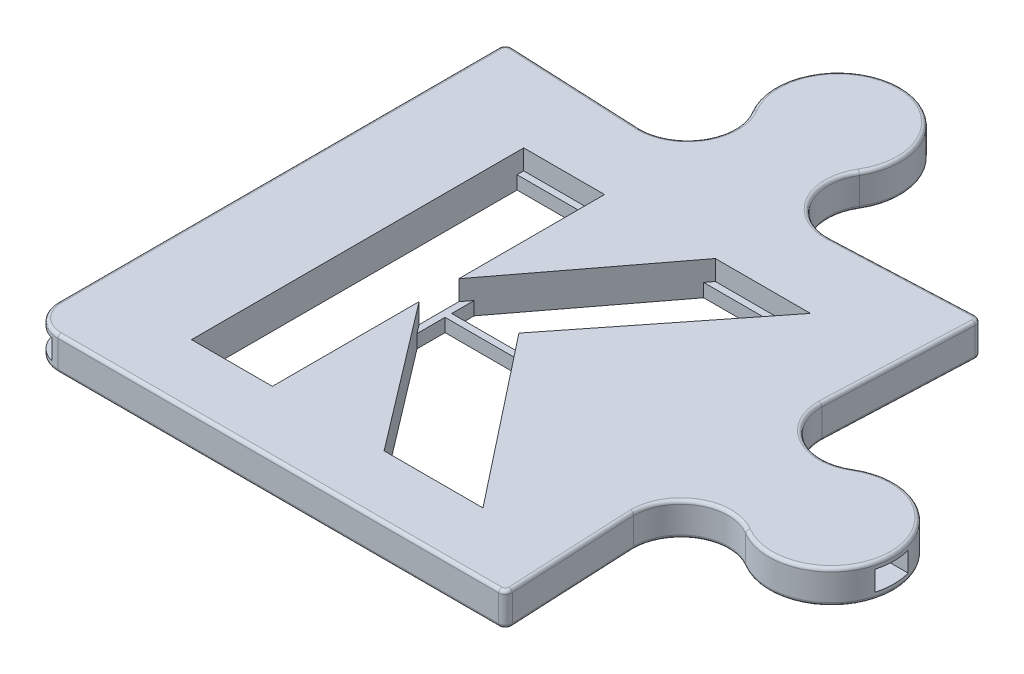
SolidWorks part; units mm, degrees
ref_plane "Front Plane" through (0, 0, 0) normal (0, 0, 1) x (1, 0, 0)
ref_plane "Top Plane" through (0, 0, 0) normal (0, 1, 0) x (1, 0, 0)
ref_plane "Right Plane" through (0, 0, 0) normal (1, 0, 0) x (0, 0, -1)
sketch "Sketch1" plane through (0, 0, 0) normal (0, 1, 0) x (1, 0, 0)
  line L0 (-31, -36) -> (37, -36) construction
  line L1 (-36, 37) -> (-36, -31) construction
  line L2 (-14.1421, 36) -> (-36, 37) construction
  line L3 (37, 37) -> (14.1421, 36) construction
  line L4 (36, 13.1421) -> (37, 37) construction
  line L5 (37, -36) -> (36, -15.1421) construction
  line L6 (-35.4, 36.3719) -> (-35.4, -31)
  line L7 (-36, 36) -> (36, 36) construction
  line L8 (-36, 36) -> (-36, -36) construction
  line L9 (-36, -36) -> (36, -36) construction
  line L10 (36, 36) -> (36, -36) construction
  line L11 (-31, -35.4) -> (36.3705, -35.4)
  line L12 (36.3705, -35.4) -> (35.4, -15.1568)
  line L13 (35.4, 13.155) -> (36.3732, 36.372)
  line L14 (36.3732, 36.372) -> (14.1555, 35.4)
  line L15 (-14.1562, 35.4) -> (-35.4, 36.3719)
  line L16 (-30, -24) -> (30, -24) construction
  line L17 (-30, 29) -> (30, 29) construction
  line L18 (-30, 29) -> (-30, -31) construction
  line L19 (-30, -31) -> (30, -31) construction
  line L20 (30, 29) -> (30, -31) construction
  line L21 (-30, 24) -> (30, 24) construction
  line L22 (-30, 24) -> (-30, -26) construction
  line L23 (-30, -26) -> (30, -26) construction
  line L24 (30, 24) -> (30, -26) construction
  arc A0 (-36, -31) -> (-31, -36) centre (-31, -31) ccw construction
  arc A1 (-14.1421, 36) -> (-8.571, 45.8485) centre (-14.1421, 42.5) ccw construction
  arc A2 (8.571, 45.8485) -> (-8.571, 45.8485) centre (0, 51) ccw construction
  arc A3 (8.571, 45.8485) -> (14.1421, 36) centre (14.1421, 42.5) ccw construction
  arc A4 (36, 13.1421) -> (45.8485, 7.571) centre (42.5, 13.1421) ccw construction
  arc A5 (45.8485, -9.571) -> (45.8485, 7.571) centre (51, -1) ccw construction
  arc A6 (45.8485, -9.571) -> (36, -15.1421) centre (42.5, -15.1421) ccw construction
  arc A7 (-35.4, -31) -> (-31, -35.4) centre (-31, -31) ccw
  arc A8 (46.1576, -9.0567) -> (35.4, -15.1568) centre (42.5, -15.1421) ccw
  arc A9 (46.1576, -9.0567) -> (46.1576, 7.0567) centre (51, -1) ccw
  arc A10 (35.4, 13.155) -> (46.1576, 7.0567) centre (42.5, 13.1421) ccw
  arc A11 (8.0567, 46.1576) -> (14.1555, 35.4) centre (14.1421, 42.5) ccw
  arc A12 (8.0567, 46.1576) -> (-8.0567, 46.1576) centre (0, 51) ccw
  arc A13 (-14.1562, 35.4) -> (-8.0567, 46.1576) centre (-14.1421, 42.5) ccw
  point P32 (36, 0)
  point P34 (0, 36)
  dimension "D5" = 6.5
  dimension "D6" = 10
  dimension "D7" = 6.5
  dimension "D13" = 5
  dimension "D9" = 10
  dimension "D11" = 6.5
  dimension "D12" = 6.5
  dimension "D1" = 72
  dimension "D2" = 1
  dimension "D3" = 1
  dimension "D4" = 15
  dimension "D8" = 1
  dimension "D10" = 35
  dimension "D14" = 15
  dimension "D15" = 36
  dimension "D16" = 1
  dimension "D18" = 60
  dimension "D19" = 60
  dimension "D20" = 5
  dimension "D21" = 6
  dimension "D22" = 5
  dimension "D23" = 50
  dimension "D24" = 2
  dimension "D17" = 0.6
extrude "Boss-Extrude1" add sketch "Sketch1" along normal blind 5
sketch "Sketch6" plane through (0, 0, 0) normal (0, -1, 0) x (1, 0, 0)
  line L0 (-35.4, -36.3719) -> (-35.4, 31) construction
  line L1 (-35.4, 17.9) -> (-27.4, 17.9)
  line L2 (-35.4, 17.9) -> (-35.4, -16.1)
  line L3 (-35.4, -16.1) -> (-27.4, -16.1)
  line L4 (-27.4, 17.9) -> (-27.4, -16.1)
  line L5 (-31, 35.4) -> (36.3705, 35.4) construction
  line L6 (-35.4, 14.65) -> (-30.4, 14.65)
  line L7 (-35.4, 14.65) -> (-35.4, -12.85)
  line L8 (-35.4, -12.85) -> (-30.4, -12.85)
  line L9 (-30.4, 14.65) -> (-30.4, -12.85)
  point P15 (-27.4, 0.9)
  point P16 (-30.4, 0.9)
  line M28 (-35.4, 31) -> (-35.4, -36.3719)
  dimension "D1" = 8
  dimension "D2" = 20.75
  dimension "D3" = 27.5
  dimension "D4" = 5
  dimension "D5" = 34
extrude "Cut-Extrude3" cut sketch "Sketch6" against normal blind 3 from offset 1 contours L6 L9 L8 L3 L4 L1 M28 | L9 L6 L2 L8 region at (-29.8665, 0, 0.9) region at (-32.9, 0, 0.9) offset against normal yes
extrude "Cut-Extrude4" cut sketch "Sketch6<3>" against normal up to next contours L9 L6 L2 L8 region at (-32.9, 0, 0.9)
sketch "Sketch6<3>" plane through (0, 0, 0) normal (0, -1, 0) x (1, 0, 0) same geometry as "Sketch6"
sketch "Sketch8" plane through (0, 0, 0) normal (0, -1, 0) x (1, 0, 0)
  line L1 (-2.5, -51.4) -> (2.5, -51.4)
  line L2 (-2.5, -51.4) -> (-2.5, -60.4)
  line L3 (-2.5, -60.4) -> (2.5, -60.4)
  line L4 (2.5, -51.4) -> (2.5, -60.4)
  line L5 (51.4, 3.5) -> (60.4, 3.5)
  line L6 (51.4, 3.5) -> (51.4, -1.5)
  line L7 (51.4, -1.5) -> (60.4, -1.5)
  line L8 (60.4, 3.5) -> (60.4, -1.5)
  arc A0 (-8.0567, -46.1576) -> (8.0567, -46.1576) centre (0, -51) ccw construction
  arc A1 (46.1576, -7.0567) -> (46.1576, 9.0567) centre (51, 1) ccw construction
  point P4 (0, -60.4)
  point P13 (60.4, 1)
  dimension "D1" = 5
  dimension "D2" = 9
  dimension "D3" = 5
  dimension "D4" = 9
extrude "Cut-Extrude5" cut sketch "Sketch8" against normal blind 3 from offset 1 offset against normal yes
sketch "Sketch9" plane through (0, 0, 0) normal (0, -1, 0) x (1, 0, 0)
  line L0 (-31, 35.4) -> (36.3705, 35.4) construction
  line L1 (-35.4, 14.65) -> (-35.4, 31) construction
  line L2 (-31.7636, 35.3332) -> (-35.4, 31) construction
  line L3 (-33.2571, 29.735) -> (-30.0429, 33.565) construction
  line L4 (-30.0429, 33.565) -> (-33.2571, 29.735) construction
  line L5 (-30.0429, 33.565) -> (-32.7119, 35.8048)
  line L6 (-33.2571, 29.735) -> (-35.926, 31.9747)
  line L7 (-32.7119, 35.8048) -> (-35.926, 31.9747)
  circle A0 centre (-31.65, 31.65) radius 2.5
  arc A1 (-31, 35.4) -> (-35.4, 31) centre (-31, 31) ccw construction
  arc M41 (-31, 35.4) -> (-35.4, 31) centre (-31, 31) ccw
  dimension "D1" = 5
  dimension "D3" = 3.75
  dimension "D4" = 5.6569
  dimension "D2" = 3.75
extrude "Cut-Extrude6" cut sketch "Sketch9" against normal blind 3 from offset 1 contours A0 L5 L6 M41 | A0 L5 region at (-33.6239, 0, 33.3064) region at (-31.65, 0, 31.65) offset against normal yes
sketch "Sketch11" plane through (-35.4, 0, 0) normal (-1, 0, 0) x (0, 0, 1)
  line L0 (-13.155, 0) -> (-36.372, 0) construction
  line L1 (-25.1, 3) -> (-19.1, 3)
  line L2 (-25.1, 3) -> (-25.1, 1.5)
  line L3 (-25.1, 1.5) -> (-19.1, 1.5)
  line L4 (-19.1, 3) -> (-19.1, 1.5)
  line L5 (-16.1, 4) -> (-16.1, 1) construction
  line L6 (35.4, 0) -> (15.1568, 0) construction
  line L7 (20.9, 3) -> (26.9, 3)
  line L8 (20.9, 3) -> (20.9, 1.5)
  line L9 (20.9, 1.5) -> (26.9, 1.5)
  line L10 (26.9, 3) -> (26.9, 1.5)
  line L12 (17.9, 4) -> (17.9, 1) construction
  dimension "D1" = 3
  dimension "D2" = 1.5
  dimension "D3" = 3
  dimension "D4" = 6
  dimension "D5" = 3
  dimension "D6" = 1.5
  dimension "D7" = 6
  dimension "D8" = 3
fillet "Fillet1" radius 0.5 17 edges at (-35.4, 0, 22.825) (-34.1113, 0, 34.1113) (2.6853, 0, 35.4) (35.8853, 0, 25.2784) (38.9978, 0, 8.966) (60.4, 0, 1) (38.9986, 0, -6.9655) (35.8866, 0, -24.7635) (25.2643, 0, -35.886) (7.9657, 0, -38.9984) (0, 0, -60.4) (-7.9658, 0, -38.9981) (-24.7781, 0, -35.886) (-35.4, 0, -24.611) (-32.9, 0, -12.85) (-30.4, 0, 0.9) (-32.9, 0, 14.65)
fillet "Fillet2" radius 0.5 13 edges at (-7.9658, 5, -38.9981) (0, 5, -60.4) (7.9657, 5, -38.9984) (25.2643, 5, -35.886) (35.8866, 5, -24.7635) (38.9986, 5, -6.9655) (60.4, 5, 1) (38.9978, 5, 8.966) (35.8853, 5, 25.2784) (2.6853, 5, 35.4) (-34.1113, 5, 34.1113) (-35.4, 5, -2.686) (-24.7781, 5, -35.886)
fillet "Fillet3" radius 1 9 edges at (36.2202, 0.1464, -36.2187) (36.2202, 4.8536, -36.2187) (36.3732, 2.5, -36.372) (-35.2536, 0.1464, -36.2186) (-35.2536, 4.8536, -36.2186) (36.2169, 0.1464, 35.2536) (36.2169, 4.8536, 35.2536) (36.3705, 2.5, 35.4) (-35.4, 2.5, -36.3719)
extrude "Cut-Extrude9" cut sketch "Sketch11" against normal blind 3
chamfer "Chamfer1" distance 1 angle 50 2 edges at (-35.4, 1.5, 23.9) (-35.4, 1.5, -22.1) first distance on face at (-35.4, 2.25, -22.1)
sketch "Sketch12" plane through (0, 5, 0) normal (0, 1, 0) x (1, 0, 0)
  text T0 "K" font "Poppins" height 50
extrude "Cut-Extrude10" cut sketch "Sketch12" against normal through all
sketch "Sketch13" plane through (0, 0, 0) normal (0, -1, 0) x (1, 0, 0)
  line L0 (8.6768, 26) -> (-8.141, 3.9163) construction
  line L1 (-7.141, 5.2294) -> (-8.141, 5.2294)
  line L2 (-7.141, 5.2294) -> (-7.141, -3.3764)
  line L3 (-7.141, -3.3764) -> (-8.141, -3.3764)
  line L4 (-8.141, 5.2294) -> (-8.141, -3.3764)
  line L5 (-8.141, -24) -> (-8.141, -2.0606) construction
  line L6 (-8.141, -2.0606) -> (8.5326, -24) construction
  line L7 (3.4728, 0.5054) -> (23.5573, 26) construction
  line L8 (22.8462, -24) -> (3.4728, 0.5054) construction
  line L9 (3.8674, 1.0062) -> (-8.141, 1.0062)
  line L10 (3.8674, 1.0062) -> (3.8674, 0.0062)
  line L11 (3.8674, 0.0062) -> (-8.141, 0.0062)
  line L12 (-8.141, 1.0062) -> (-8.141, 0.0062)
  line L13 (-8.141, 3.9163) -> (-8.141, 26) construction
  line L14 (-20.3112, 26) -> (-8.141, 26)
  line L15 (-20.3112, 26) -> (-20.3112, 25)
  line L16 (-20.3112, 25) -> (-8.141, 25)
  line L17 (-8.141, 26) -> (-8.141, 25)
  line L18 (-20.3112, 26) -> (-20.3112, -24) construction
  line L19 (7.9153, 25) -> (23.5573, 25)
  line L20 (7.9153, 25) -> (7.9153, 26)
  line L21 (7.9153, 26) -> (23.5573, 26)
  line L22 (23.5573, 25) -> (23.5573, 26)
  line L23 (-8.141, -23) -> (-20.3112, -23)
  line L24 (-8.141, -23) -> (-8.141, -24)
  line L25 (-8.141, -24) -> (-20.3112, -24)
  line L26 (-20.3112, -23) -> (-20.3112, -24)
  line L28 (22.8462, -23) -> (7.7726, -23)
  line L29 (22.8462, -23) -> (22.8462, -24)
  line L30 (22.8462, -24) -> (7.7726, -24)
  line L31 (7.7726, -23) -> (7.7726, -24)
  line M39 (8.6768, 26) -> (23.5573, 26)
  line M40 (23.5573, 26) -> (3.4728, 0.5054)
  line M41 (3.4728, 0.5054) -> (22.8462, -24)
  line M42 (22.8462, -24) -> (8.5326, -24)
  line M43 (8.5326, -24) -> (-8.141, -2.0606)
  line M44 (-8.141, -2.0606) -> (-8.141, -24)
  line M45 (-8.141, -24) -> (-20.3112, -24)
  line M46 (-20.3112, -24) -> (-20.3112, 26)
  line M49 (-8.141, 3.9163) -> (8.6768, 26)
  dimension "D1" = 1
  dimension "D2" = 1
  dimension "D3" = 1
  dimension "D4" = 1
  dimension "D5" = 1
  dimension "D6" = 1
extrude "Boss-Extrude2" add sketch "Sketch13" against normal blind 2 contours L19 M49 M40 M39 | L28 M41 M43 M42 | L23 M44 M46 M45 | L2 L3 L4 L1 | L9 L12 L11 L10 | L16 L17 L14 L15 region at (-14.2261, 0, -23.5) region at (15.7298, 0, 25.5001) region at (15.3019, 0, -23.5002)
